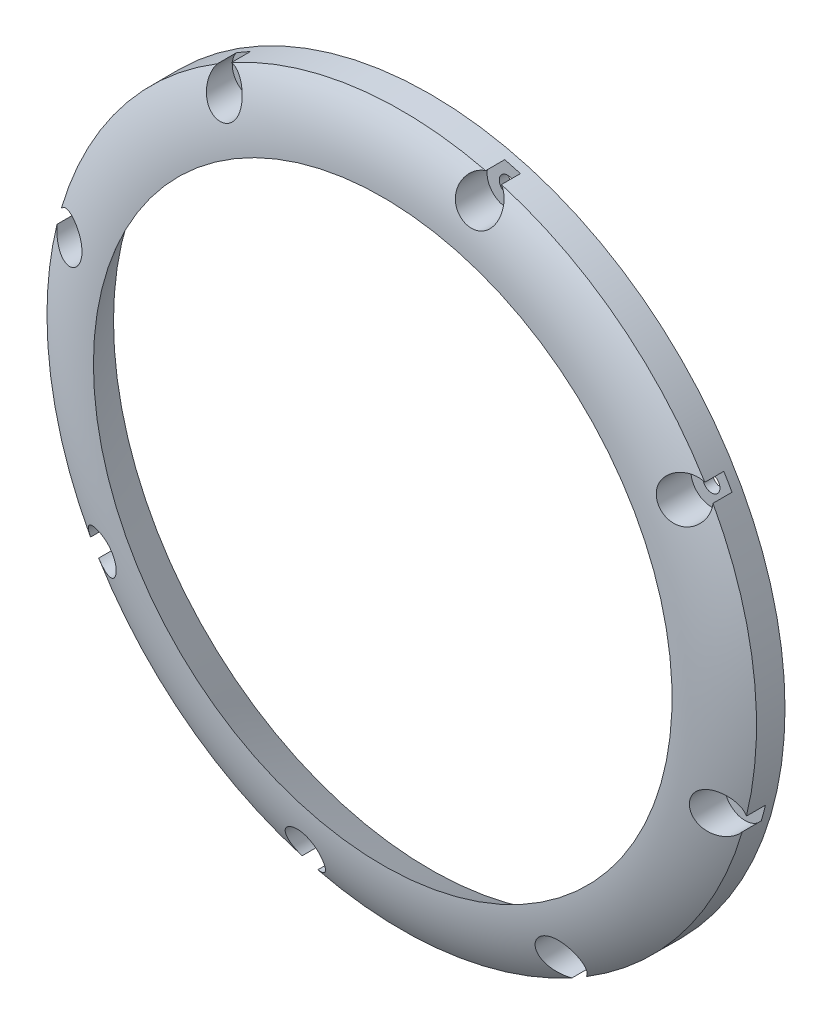
SolidWorks part; units mm, degrees
material "PUR"
ref_plane "Front Plane" through (0, 0, 0) normal (0, 0, 1) x (1, 0, 0)
ref_plane "Top Plane" through (0, 0, 0) normal (0, 1, 0) x (1, 0, 0)
ref_plane "Right Plane" through (0, 0, 0) normal (1, 0, 0) x (0, 0, -1)
sketch "Sketch1" plane through (0, 0, 0) normal (0, 0, 1) x (1, 0, 0)
  circle A0 centre (0, 0) radius 100 construction
  circle A1 centre (0, 0) radius 100
  circle A2 centre (0, 0) radius 112
  arc A3 (111.914, 4.3889) -> (-77.2845, 81.0624) centre (0, 0) ccw construction
sketch "Sketch2" plane through (0, 0, 0) normal (0, 1, 0) x (1, 0, 0)
  line L0 (-112, 0) -> (112, 0) construction
  line L1 (-100, 0) -> (100, 0) construction
  line L2 (-112, 0) -> (112, 0) construction
  line L3 (-100, 0) -> (100, 0) construction
  line L4 (-100, 0) -> (-112, 0)
  line L5 (-100, 0) -> (-91.3397, -15)
  line L6 (0, 0) -> (0, -15) construction
  line L7 (-112, 0) -> (-112, -9)
  line L8 (-91.3397, -15) -> (0, -15) construction
  arc A0 (-91.3397, -15) -> (-112, -9) centre (-91.3397, 23.5705) cw
  dimension "D1" = 60
  dimension "D2" = 9
  dimension "D3" = 15
revolve "Revolve1" add sketch "Sketch2" angle 360 about L6
sketch "Sketch3" plane through (0, 0, 0) normal (0, 0, -1) x (-1, 0, 0)
  circle A0 centre (-102.3881, -27.4348) radius 2.65 construction
  circle A1 centre (-102.3881, -27.4348) radius 2.65
extrude "Cut-Extrude1" cut sketch "Sketch3" against normal through all
sketch "Sketch4" plane through (0, 0, 0) normal (0, 0, -1) x (-1, 0, 0)
  circle A0 centre (-102.3881, -27.4348) radius 6.5
  dimension "D1" = 13
extrude "Cut-Extrude2" cut sketch "Sketch4" against normal through all from offset 3 offset against normal yes
pattern_circular "CirPattern1" count 8 over 360 of "Cut-Extrude1", "Cut-Extrude2"
